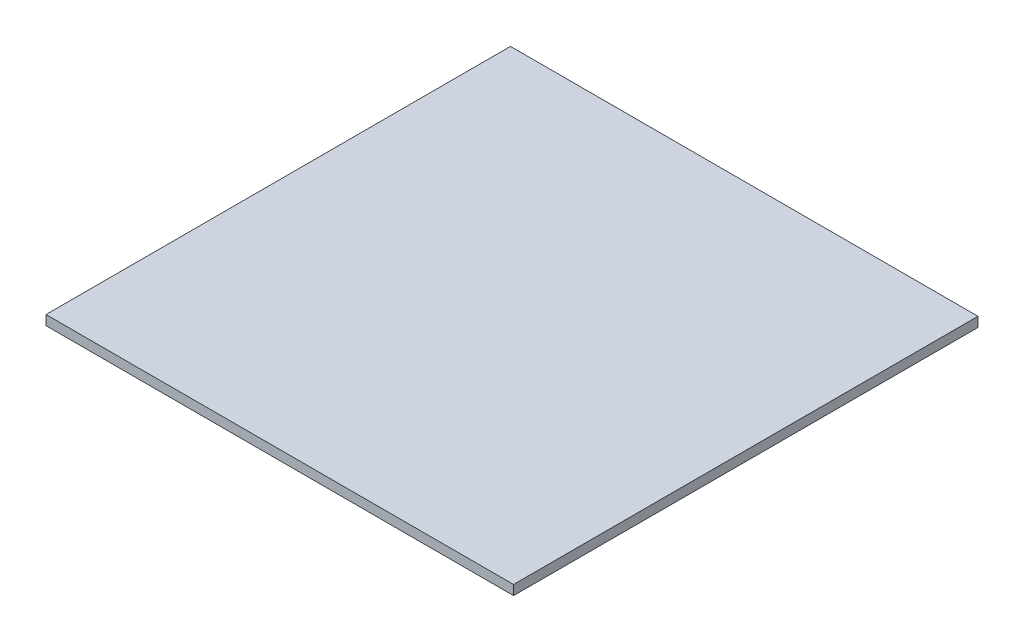
SolidWorks part; units mm, degrees
ref_plane "Front Plane" through (0, 0, 0) normal (0, 0, 1) x (1, 0, 0)
ref_plane "Top Plane" through (0, 0, 0) normal (0, 1, 0) x (1, 0, 0)
ref_plane "Right Plane" through (0, 0, 0) normal (1, 0, 0) x (0, 0, -1)
sketch "Sketch2" plane through (0, 0, 0) normal (0, 1, 0) x (1, 0, 0)
  circle A0 centre (0, 0) radius 60
extrude "Boss-Extrude1" add sketch "Sketch2" along normal blind 36
sketch "Sketch3" plane through (0, 36, 0) normal (0, 1, 0) x (1, 0, 0)
  line L1 (-142.811, 150.7577) -> (147.189, 150.7577)
  line L2 (-142.811, 150.7577) -> (-142.811, -137.3508)
  line L3 (-142.811, -137.3508) -> (147.189, -137.3508)
  line L4 (147.189, 150.7577) -> (147.189, -137.3508)
extrude "Boss-Extrude2" add sketch "Sketch3" along normal blind 6
